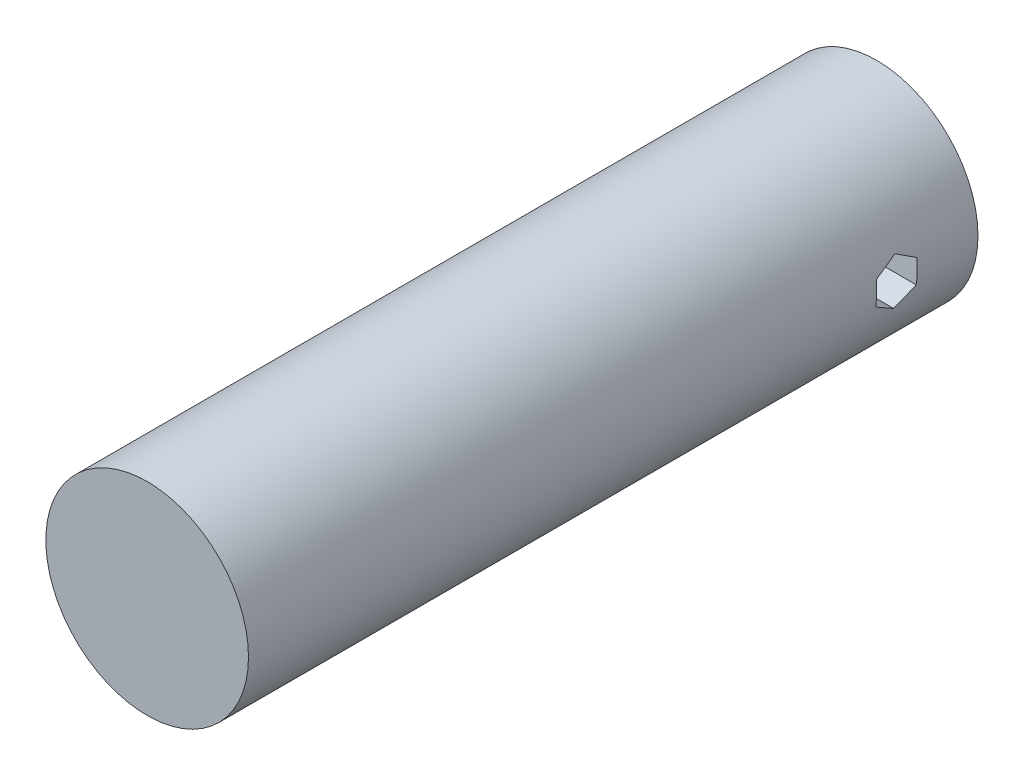
SolidWorks part; units mm, degrees
ref_plane "Front Plane" through (0, 0, 0) normal (0, 0, 1) x (1, 0, 0)
ref_plane "Top Plane" through (0, 0, 0) normal (0, 1, 0) x (1, 0, 0)
ref_plane "Right Plane" through (0, 0, 0) normal (1, 0, 0) x (0, 0, -1)
sketch "Sketch1" plane through (0, 0, 0) normal (0, 0, 1) x (1, 0, 0)
  circle A0 centre (0, 0) radius 6.25
  dimension "D1" = 12.5
extrude "Boss-Extrude1" add sketch "Sketch1" along normal blind 45
sketch "Sketch2" plane through (0, 0, 0) normal (0, 0, -1) x (-1, 0, 0)
  line L0 (1.8, 0) -> (-0.94, 0) construction
  line L1 (-0.94, 1.5351) -> (-0.94, -1.5351)
  arc A0 (-0.94, -1.5351) -> (-0.94, 1.5351) centre (0, 0) ccw
  point P7 (-0.94, 0)
  dimension "D1" = 3.6
  dimension "D2" = 2.74
extrude "Cut-Extrude1" cut sketch "Sketch2" against normal blind 10
sketch "Sketch3" plane through (0.94, 0, 0) normal (-1, 0, 0) x (0, 0, 1)
  line L0 (0, 1.5351) -> (0, -1.5351) construction
  line L1 (6.2307, 0.7541) -> (4.9623, 1.4429)
  line L2 (4.9623, 1.4429) -> (3.7316, 0.6888)
  line L3 (3.7316, 0.6888) -> (3.7693, -0.7541)
  line L4 (3.7693, -0.7541) -> (5.0377, -1.4429)
  line L5 (5.0377, -1.4429) -> (6.2684, -0.6888)
  line L6 (6.2684, -0.6888) -> (6.2307, 0.7541)
  line L8 (0, 0) -> (5, 0) construction
  circle A1 centre (5, 0) radius 1.25 construction
  dimension "D1" = 2.5
  dimension "D2" = 5
  dimension "D3" = 1.4429
extrude "Cut-Extrude2" cut sketch "Sketch3" against normal through all
